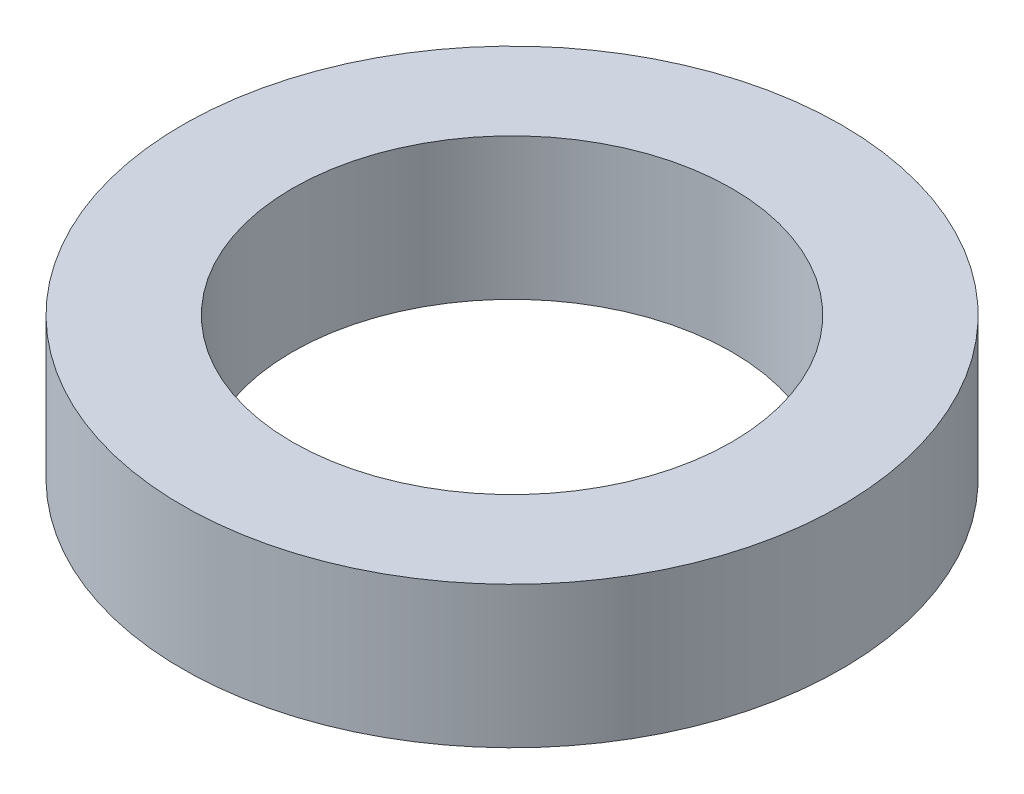
SolidWorks part; units mm, degrees
ref_plane "Front Plane" through (0, 0, 0) normal (0, 0, 1) x (1, 0, 0)
ref_plane "Top Plane" through (0, 0, 0) normal (0, 1, 0) x (1, 0, 0)
ref_plane "Right Plane" through (0, 0, 0) normal (1, 0, 0) x (0, 0, -1)
sketch "Sketch1" plane through (0, 0, 0) normal (0, 1, 0) x (1, 0, 0)
  circle A0 centre (0, 0) radius 67.5
  dimension "FLANGE_OD" = 135
extrude "Boss-Extrude1" add sketch "Sketch1" along normal blind 29
sketch "Sketch2" plane through (0, 0, 0) normal (0, 1, 0) x (1, 0, 0)
  circle A0 centre (0, 0) radius 45
  dimension "BORE_D" = 90
extrude "Cut-Extrude1" cut sketch "Sketch2" along normal through all
sketch "Sketch3" plane through (0, 29, 0) normal (0, 1, 0) x (1, 0, 0)
  circle A0 centre (0, 0) radius 26.6517 construction
  circle A1 centre (-26.6517, 0) radius 2.9167
  dimension "BOLT_D" = 5.8334
  dimension "BOLT_PCD" = 53.3035
extrude "Cut-Extrude2" cut sketch "Sketch3" against normal blind 22.8705 rebuild error yes
pattern_circular "CirPattern1" count 6 over 360 rebuild error yes
